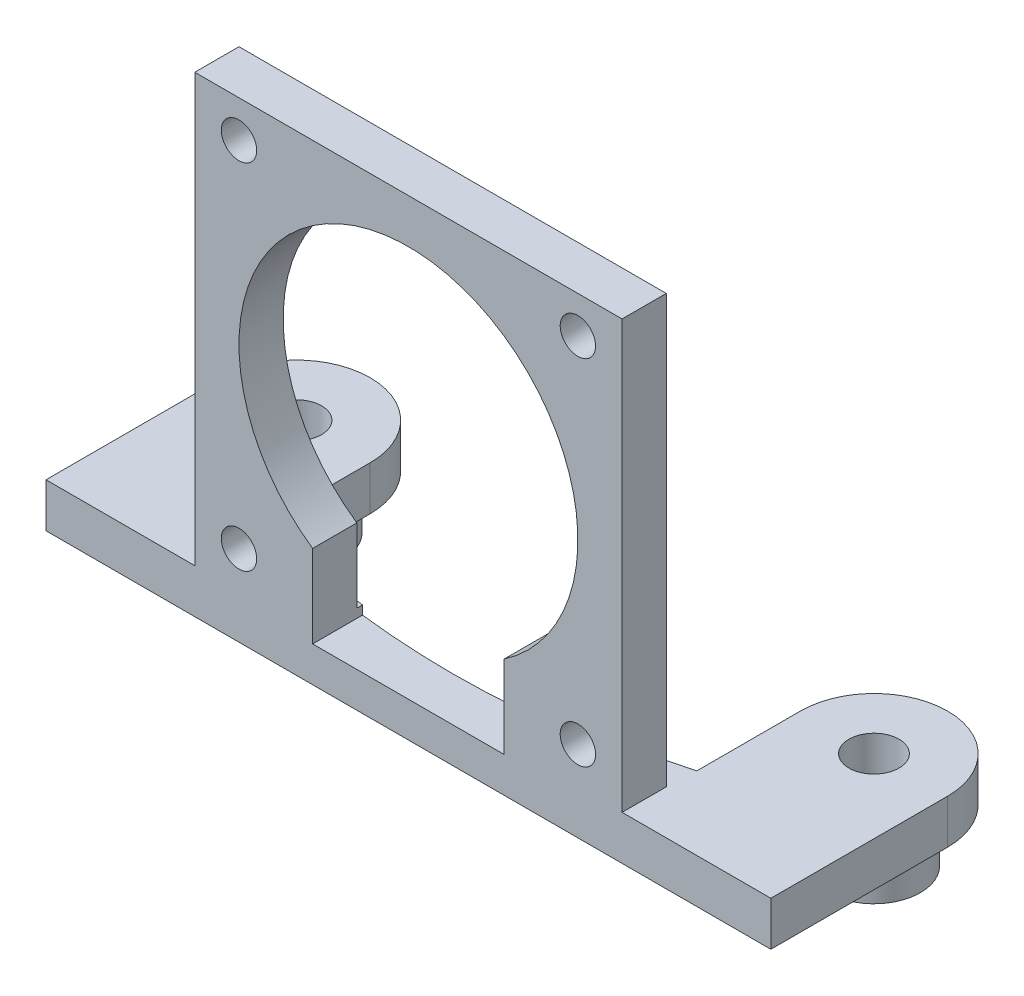
SolidWorks part; units mm, degrees
note: The reader was unsure of these and kept them because the rebuilt part matched: shared geometry of "Sketch1<7>", "Sketch1<5>".
ref_plane "Front Plane" through (0, 0, 0) normal (0, 0, 1) x (1, 0, 0)
ref_plane "Top Plane" through (0, 0, 0) normal (0, 1, 0) x (1, 0, 0)
ref_plane "Right Plane" through (0, 0, 0) normal (1, 0, 0) x (0, 0, -1)
sketch "Sketch1" plane through (0, 0, 0) normal (0, 1, 0) x (1, 0, 0)
  line L0 (0, -1000) -> (0, 49000) construction
  line L1 (14.5959, -46) -> (14.5959, -55)
  line L2 (-14.5, -55) -> (14.5, -55)
  line L3 (-14.5, -55) -> (-14.5, -58)
  line L4 (-14.5, -58) -> (14.5, -58)
  line L5 (14.5, -55) -> (14.5, -58)
  line L6 (-14.5, -55) -> (14.5, -58) construction
  line L7 (-14.5, -58) -> (14.5, -55) construction
  line L8 (-24.5959, -46) -> (-24.5959, -54.4912)
  line L9 (24.5959, -46) -> (24.5959, -54.4912)
  line L10 (24.5959, -54.4912) -> (24.5959, -58)
  line L11 (24.5959, -58) -> (-24.5959, -58)
  line L12 (-14.5959, -46) -> (-14.5959, -55)
  line L13 (-24.5959, -58) -> (-24.5959, -54.4912)
  circle A0 centre (0, 0) radius 50 construction
  circle A1 centre (-19.5959, -46) radius 3.15
  circle A2 centre (0, -50) radius 3.15 construction
  circle A3 centre (19.5959, -46) radius 3.15
  arc A4 (-24.5959, -49.1939) -> (24.5959, -49.1939) centre (0, 0) ccw
  circle A5 centre (-19.5959, -46) radius 5
  circle A6 centre (19.5959, -46) radius 5
  circle A7 centre (-19.5959, -46) radius 1.7
  circle A8 centre (19.5959, -46) radius 1.7
  arc A9 (-24.5959, -54.4912) -> (-14.5, -58) centre (0, 0) ccw
  arc A10 (14.5, -58) -> (24.5959, -54.4912) centre (0, 0) ccw
  point P16 (0, -56.5)
  dimension "D1" = 100
  dimension "D2" = 6.3
  dimension "D4" = 110
  dimension "D5" = 3.4
  dimension "D3" = 20
  dimension "D6" = 29
  dimension "D7" = 3
  dimension "D8" = 58
extrude "Boss-Extrude2" add sketch "Sketch1" against normal blind 3 contours L8 A9 L3 L2 L12 A4 | A1 A7 | A5 A1 | A5 L8 A4 | A5 A4 L12 | A4 L12 L2 L1 | L5 L2 L3 L4 | L5 A10 L9 A4 L1 L2 | A4 A6 L1 | A6 A3 | L9 A6 A4 | A3 A8 | A9 L13 L11 | A10 L11 L10
extrude "Boss-Extrude4" add sketch "Sketch1<7>" along normal blind 29 from surface at 0 contours L5 L2 L3 L4 starting at face at (0, 0, 49.7535)
sketch "Sketch1<7>" plane through (0, 0, 0) normal (0, 1, 0) x (1, 0, 0) same geometry as "Sketch1"
sketch "Sketch2" plane through (0, 0, 58) normal (0, 0, 1) x (1, 0, 0)
  line L1 (0, -1000) -> (0, 49000) construction
  line L2 (14.5, 29) -> (14.5, 0) construction
  line L3 (-14.5, 14.5) -> (14.5, 14.5) construction
  line L4 (11.5, 2.5) -> (-11.5, 2.5) construction
  line L5 (11.5, 2.5) -> (11.5, 26.5) construction
  line L6 (11.5, 26.5) -> (-11.5, 26.5) construction
  line L7 (-11.5, 2.5) -> (-11.5, 26.5) construction
  line L8 (11.5, 2.5) -> (-11.5, 26.5) construction
  line L9 (11.5, 26.5) -> (-11.5, 2.5) construction
  line L10 (-6.5, 0) -> (6.5, 0)
  line L11 (-6.5, 0) -> (-6.5, 7)
  line L12 (-6.5, 7) -> (6.5, 7)
  line L13 (6.5, 0) -> (6.5, 7)
  line L14 (-6.5, 0) -> (6.5, 0)
  line L15 (-6.5, 0) -> (-6.5, -0.6)
  line L16 (-6.5, -0.6) -> (6.5, -0.6)
  line L17 (6.5, 0) -> (6.5, -0.6)
  circle A0 centre (-11.5, 2.5) radius 1.2
  circle A1 centre (-11.5, 26.5) radius 1.2
  circle A2 centre (11.5, 2.5) radius 1.2
  circle A3 centre (11.5, 26.5) radius 1.2
  circle A4 centre (0, 14.5) radius 11.5
  point P25 (14.5, 14.5)
  dimension "D2" = 2.4
  dimension "D5" = 7
  dimension "D4" = 23
  dimension "D1" = 24
  dimension "D3" = 23
  dimension "D6" = 13
  dimension "D7" = 0.6
extrude "Cut-Extrude1" cut sketch "Sketch2" against normal up to next contours A4 | A3 | A1 | A0 | L10 L13 L12 L11 | L17 L10 L15 L16 | A2 | L12 A4
extrude "Boss-Extrude3" add sketch "Sketch1<5>" against normal blind 3.6 from surface at -3 contours A1 A7 | A3 A8 | L3 L2 L5 L4
sketch "Sketch1<5>" plane through (0, 0, 0) normal (0, 1, 0) x (1, 0, 0) same geometry as "Sketch1"
